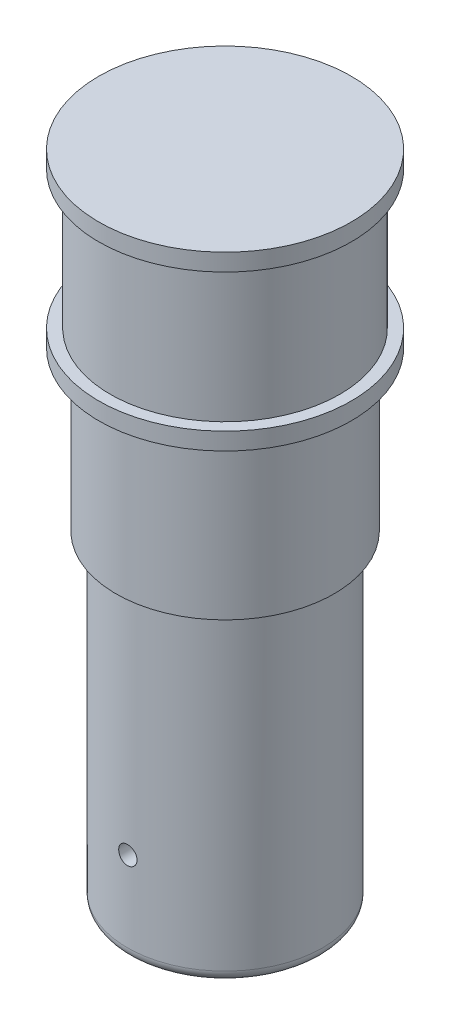
SolidWorks part; units mm, degrees
material "ABS"
ref_plane "Front Plane" through (0, 0, 0) normal (0, 0, 1) x (1, 0, 0)
ref_plane "Top Plane" through (0, 0, 0) normal (0, 1, 0) x (1, 0, 0)
ref_plane "Right Plane" through (0, 0, 0) normal (1, 0, 0) x (0, 0, -1)
sketch "Sketch1" plane through (0, 0, 0) normal (0, 0, 1) x (1, 0, 0)
  line L2 (-8.5, -42) -> (-8.5, -13.8)
  line L3 (-9.5, 0) -> (-11, 0)
  line L4 (-11, 0) -> (-11, 1.5)
  line L5 (-11, 1.5) -> (-10, 1.5)
  line L6 (-10, 1.5) -> (-10, 13.5)
  line L7 (-10, 13.5) -> (-11, 13.5)
  line L8 (-11, 13.5) -> (-11, 15)
  line L9 (-11, 15) -> (0, 15)
  line L10 (0, 15) -> (0, -28)
  line L11 (-4, -42) -> (-8.5, -42)
  line L12 (-4, -28) -> (-4, -42)
  line L13 (0, -28) -> (-4, -28)
  line L14 (-8.5, -13.8) -> (-9.5, -13.8)
  line L15 (-9.5, -13.8) -> (-9.5, 0)
  dimension "D1" = 8.5
  dimension "D2" = 1
  dimension "D3" = 42
  dimension "D4" = 1.5
  dimension "D5" = 4
  dimension "D6" = 14
  dimension "D7" = 15
  dimension "D8" = 10
  dimension "D9" = 28.2
  dimension "D10" = 1
revolve "Revolve1" add sketch "Sketch1" angle 360 about L10
fillet "Fillet1" radius 1 2 edges at (-8.5, -42, 0) (-4, -42, 0)
hole_wizard "M2x0.4 Tapped Hole1" positions "Sketch2" profile "Sketch3" tap size "M2x0.4" standard "ANSI Metric" end condition up to next
sketch "Sketch2" plane through (0, 0, 0) normal (0, 0, 1) x (1, 0, 0)
  line L0 (-7.5, -42) -> (7.5, -42) construction
  point P0 (0, -34)
  dimension "D1" = 8
sketch "Sketch3" plane through (0, -34, 0) normal (1, 0, 0) x (0, 1, 0)
  line L0 (0, 0) -> (0, 8.5)
  line L1 (0, 8.5) -> (0.8, 8.5)
  line L2 (0.8, 8.5) -> (0.8, 0)
  line L5 (0.8, 0) -> (0, 0)
  line L11 (0, -6.35) -> (0, 107.95) construction
  dimension "Thru Tap Drill Dia." = 1.6
  dimension "Thru Tap Drill Depth" = 8.5
cosmetic thread "Hole Thread1" parameters "D2"=2
